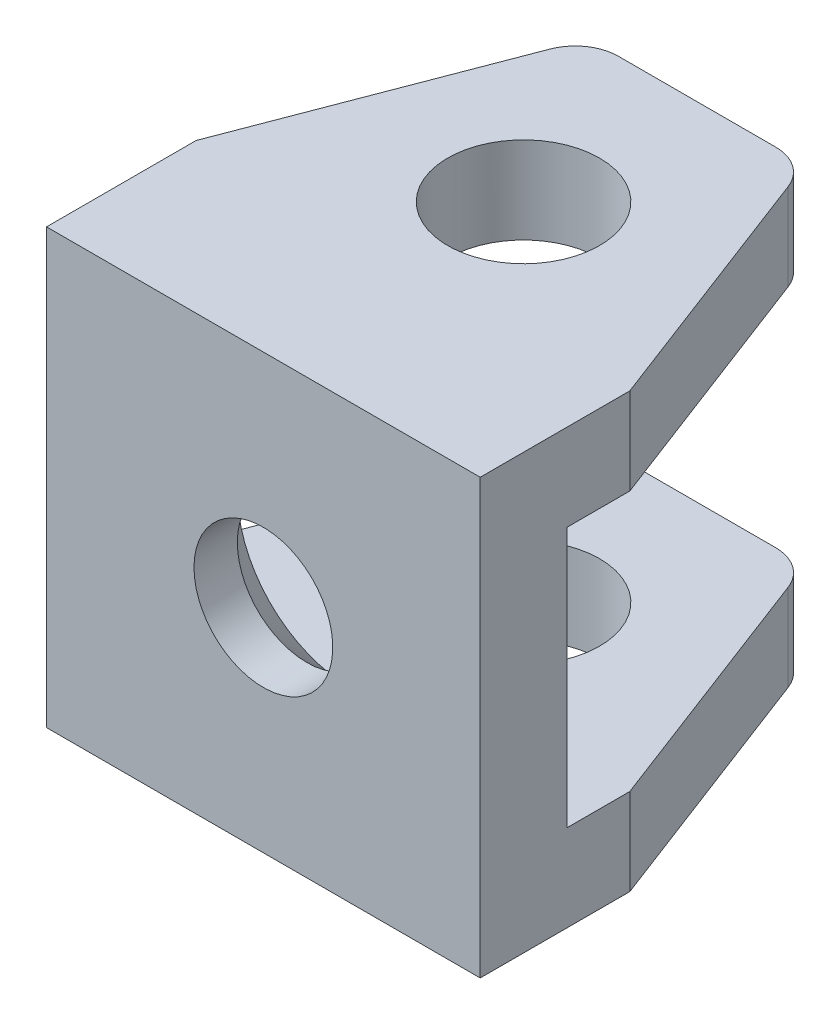
SolidWorks part; units mm, degrees
ref_plane "前视基准面" through (0, 0, 0) normal (0, 0, 1) x (1, 0, 0)
ref_plane "上视基准面" through (0, 0, 0) normal (0, 1, 0) x (1, 0, 0)
ref_plane "右视基准面" through (0, 0, 0) normal (1, 0, 0) x (0, 0, -1)
other "Configuration Table"
sketch "草图1" plane through (0, 0, 0) normal (0, 1, 0) x (1, 0, 0)
  line L0 (-2.5, 5) -> (-5, -1.5509)
  line L1 (-5, -5) -> (5, -5)
  line L2 (-5, -5) -> (-5, -1.5509)
  line L3 (-2.5, 5) -> (2.5, 5)
  line L4 (5, -5) -> (5, -1.5509)
  line L5 (-5, -5) -> (3.1905, 3.1905) construction
  line L6 (-3.1905, 3.1905) -> (5, -5) construction
  line L7 (0, 0) -> (0, 50000) construction
  line L8 (2.5, 5) -> (5, -1.5509)
  point P0 (0, 0)
  dimension "D1" = 10
  dimension "D3" = 6.5509
  dimension "D4" = 2.5
extrude "凸台-拉伸1" add sketch "草图1" along normal blind 10
sketch "草图2" plane through (5, 0, 0) normal (1, 0, 0) x (0, 0, -1)
  line L0 (5, 5) -> (-49995, 5) construction
  line L1 (5, 10) -> (5, 0) construction
  line L2 (-1.5509, 10) -> (-1.5509, 0) construction
  line L3 (5, 2) -> (5, 8)
  line L4 (5, 8) -> (-3, 8)
  line L5 (-3, 8) -> (-3, 2)
  line L6 (-1.5509, 10) -> (5, 10) construction
  line L7 (-5, 10) -> (-5, 0) construction
  line L8 (5, 2) -> (-3, 2)
  point P4 (5, 5)
  point P7 (-1.5509, 5)
  point P17 (-3, 5)
  point P18 (5, 5)
  dimension "D1" = 2
  dimension "D2" = 2
extrude "切除-拉伸1" cut sketch "草图2" against normal blind 10
sketch "草图3" plane through (0, 0, 0) normal (0, -1, 0) x (1, 0, 0)
  line L0 (-5, 5) -> (5, 5) construction
  circle A0 centre (0, -1) radius 1.75
  dimension "D2" = 3.5
  dimension "D1" = 1
  dimension "D3" = 6
extrude "切除-拉伸2" cut sketch "草图3" against normal blind 10
fillet "圆角1" radius 1 4 edges at (-2.5, 9, -5) (2.5, 9, -5) (-2.5, 1, -5) (2.5, 1, -5)
sketch "草图4" plane through (0, 0, 3) normal (0, 0, -1) x (-1, 0, 0)
  line L0 (-5, 5) -> (49985.1651, -986.6632) construction
  line L1 (-5, 8) -> (-5, 2) construction
  circle A0 centre (0, 4.9008) radius 1.6
  point P6 (-5, 5)
  dimension "D1" = 3.2
extrude "切除-拉伸3" cut sketch "草图4" against normal blind 10
chamfer "倒角1" distance 1 angle 45 1 edges at (-1.6, 4.9008, 3)
